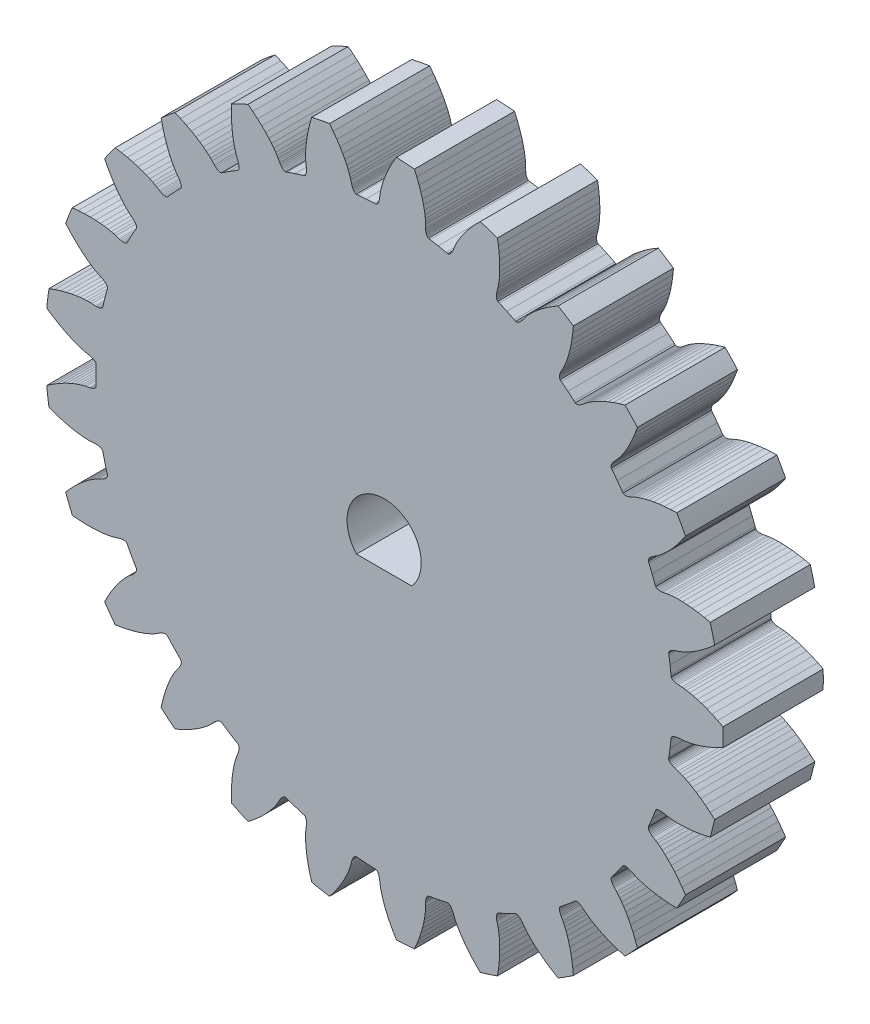
SolidWorks part; units mm, degrees
ref_plane "Front Plane" through (0, 0, 0) normal (0, 0, 1) x (1, 0, 0)
ref_plane "Top Plane" through (0, 0, 0) normal (0, 1, 0) x (1, 0, 0)
ref_plane "Right Plane" through (0, 0, 0) normal (1, 0, 0) x (0, 0, -1)
sketch "Sketch1" plane through (0, 0, 0) normal (0, 0, 1) x (1, 0, 0)
  line L0 (51.4459, 5.2739) -> (51.0519, 4.9541)
  line L1 (51.0519, 4.9541) -> (50.6785, 4.6761)
  line L2 (50.6785, 4.6761) -> (50.3269, 4.4365)
  line L3 (50.3269, 4.4365) -> (50.003, 4.2351)
  line L4 (50.003, 4.2351) -> (49.7071, 4.0679)
  line L5 (49.7071, 4.0679) -> (49.4414, 3.932)
  line L6 (49.4414, 3.932) -> (49.2085, 3.825)
  line L7 (49.2085, 3.825) -> (49.0099, 3.7435)
  line L8 (49.0099, 3.7435) -> (48.8471, 3.6846)
  line L9 (48.8471, 3.6846) -> (48.5824, 3.6)
  line L10 (48.5824, 3.6) -> (48.48, 3.5596)
  line L11 (48.48, 3.5596) -> (48.3896, 3.517)
  line L12 (48.3896, 3.517) -> (48.3112, 3.4725)
  line L13 (48.3112, 3.4725) -> (48.2449, 3.4268)
  line L14 (48.2449, 3.4268) -> (48.1907, 3.3803)
  line L15 (48.1907, 3.3803) -> (48.1486, 3.3335)
  line L16 (48.1486, 3.3335) -> (48.1186, 3.2869)
  line L17 (48.1186, 3.2869) -> (48.1007, 3.2409)
  line L18 (48.1007, 3.2409) -> (48.0947, 3.1961)
  line L19 (48.0947, 3.1961) -> (48.1121, 3.0744)
  line L20 (48.1121, 3.0744) -> (48.2057, 2.4097)
  line L21 (48.2057, 2.4097) -> (48.2803, 1.7426)
  line L22 (48.2803, 1.7426) -> (48.2938, 1.6204)
  line L23 (48.2938, 1.6204) -> (48.3107, 1.5784)
  line L24 (48.3107, 1.5784) -> (48.3395, 1.5384)
  line L25 (48.3395, 1.5384) -> (48.3802, 1.5007)
  line L26 (48.3802, 1.5007) -> (48.4326, 1.4658)
  line L27 (48.4326, 1.4658) -> (48.4966, 1.4342)
  line L28 (48.4966, 1.4342) -> (48.5722, 1.4064)
  line L29 (48.5722, 1.4064) -> (48.6592, 1.3829)
  line L30 (48.6592, 1.3829) -> (48.7573, 1.3641)
  line L31 (48.7573, 1.3641) -> (48.8666, 1.3504)
  line L32 (48.8666, 1.3504) -> (49.144, 1.3343)
  line L33 (49.144, 1.3343) -> (49.3163, 1.3177)
  line L34 (49.3163, 1.3177) -> (49.5289, 1.2882)
  line L35 (49.5289, 1.2882) -> (49.7812, 1.2424)
  line L36 (49.7812, 1.2424) -> (50.0723, 1.1769)
  line L37 (50.0723, 1.1769) -> (50.4005, 1.0885)
  line L38 (50.4005, 1.0885) -> (50.7643, 0.974)
  line L39 (50.7643, 0.974) -> (51.1644, 0.8294)
  line L40 (51.1644, 0.8294) -> (51.5953, 0.653)
  line L41 (51.5953, 0.653) -> (52.0565, 0.4412)
  line L42 (52.0565, 0.4412) -> (52.4946, 0.2183)
  line L43 (52.4946, -1.2438) -> (52.0565, -1.4667)
  line L44 (52.0565, -1.4667) -> (51.5953, -1.6785)
  line L45 (51.5953, -1.6785) -> (51.1644, -1.8549)
  line L46 (51.1644, -1.8549) -> (50.7643, -1.9995)
  line L47 (50.7643, -1.9995) -> (50.4005, -2.114)
  line L48 (50.4005, -2.114) -> (50.0723, -2.2024)
  line L49 (50.0723, -2.2024) -> (49.7812, -2.2679)
  line L50 (49.7812, -2.2679) -> (49.5289, -2.3137)
  line L51 (49.5289, -2.3137) -> (49.3163, -2.3432)
  line L52 (49.3163, -2.3432) -> (49.144, -2.3598)
  line L53 (49.144, -2.3598) -> (48.8666, -2.3759)
  line L54 (48.8666, -2.3759) -> (48.7573, -2.3896)
  line L55 (48.7573, -2.3896) -> (48.6592, -2.4084)
  line L56 (48.6592, -2.4084) -> (48.5722, -2.4319)
  line L57 (48.5722, -2.4319) -> (48.4966, -2.4597)
  line L58 (48.4966, -2.4597) -> (48.4326, -2.4913)
  line L59 (48.4326, -2.4913) -> (48.3802, -2.5262)
  line L60 (48.3802, -2.5262) -> (48.3395, -2.5639)
  line L61 (48.3395, -2.5639) -> (48.3107, -2.6039)
  line L62 (48.3107, -2.6039) -> (48.2938, -2.6459)
  line L63 (48.2938, -2.6459) -> (48.2803, -2.7681)
  line L64 (48.2803, -2.7681) -> (48.2057, -3.4352)
  line L65 (48.2057, -3.4352) -> (48.1121, -4.0999)
  line L66 (48.1121, -4.0999) -> (48.0947, -4.2216)
  line L67 (48.0947, -4.2216) -> (48.1007, -4.2664)
  line L68 (48.1007, -4.2664) -> (48.1186, -4.3124)
  line L69 (48.1186, -4.3124) -> (48.1486, -4.359)
  line L70 (48.1486, -4.359) -> (48.1907, -4.4058)
  line L71 (48.1907, -4.4058) -> (48.2449, -4.4523)
  line L72 (48.2449, -4.4523) -> (48.3112, -4.498)
  line L73 (48.3112, -4.498) -> (48.3896, -4.5425)
  line L74 (48.3896, -4.5425) -> (48.48, -4.5851)
  line L75 (48.48, -4.5851) -> (48.5824, -4.6255)
  line L76 (48.5824, -4.6255) -> (48.8471, -4.7101)
  line L77 (48.8471, -4.7101) -> (49.0099, -4.769)
  line L78 (49.0099, -4.769) -> (49.2085, -4.8505)
  line L79 (49.2085, -4.8505) -> (49.4414, -4.9575)
  line L80 (49.4414, -4.9575) -> (49.7071, -5.0934)
  line L81 (49.7071, -5.0934) -> (50.003, -5.2607)
  line L82 (50.003, -5.2607) -> (50.3269, -5.462)
  line L83 (50.3269, -5.462) -> (50.6785, -5.7016)
  line L84 (50.6785, -5.7016) -> (51.0519, -5.9796)
  line L85 (51.0519, -5.9796) -> (51.4459, -6.2994)
  line L86 (51.4459, -6.2994) -> (51.8149, -6.6243)
  line L87 (51.4513, -8.0404) -> (50.9715, -8.1474)
  line L88 (50.9715, -8.1474) -> (50.4721, -8.2379)
  line L89 (50.4721, -8.2379) -> (50.0109, -8.3016)
  line L90 (50.0109, -8.3016) -> (49.5874, -8.3422)
  line L91 (49.5874, -8.3422) -> (49.2066, -8.3626)
  line L92 (49.2066, -8.3626) -> (48.8667, -8.3666)
  line L93 (48.8667, -8.3666) -> (48.5684, -8.3576)
  line L94 (48.5684, -8.3576) -> (48.3127, -8.3392)
  line L95 (48.3127, -8.3392) -> (48.0995, -8.3149)
  line L96 (48.0995, -8.3149) -> (47.9284, -8.2882)
  line L97 (47.9284, -8.2882) -> (47.6557, -8.2348)
  line L98 (47.6557, -8.2348) -> (47.5465, -8.2208)
  line L99 (47.5465, -8.2208) -> (47.4467, -8.2146)
  line L100 (47.4467, -8.2146) -> (47.3566, -8.2158)
  line L101 (47.3566, -8.2158) -> (47.2765, -8.2239)
  line L102 (47.2765, -8.2239) -> (47.2066, -8.2386)
  line L103 (47.2066, -8.2386) -> (47.1472, -8.2593)
  line L104 (47.1472, -8.2593) -> (47.0984, -8.2857)
  line L105 (47.0984, -8.2857) -> (47.0606, -8.3174)
  line L106 (47.0606, -8.3174) -> (47.0338, -8.3538)
  line L107 (47.0338, -8.3538) -> (46.9903, -8.4688)
  line L108 (46.9903, -8.4688) -> (46.7521, -9.0964)
  line L109 (46.7521, -9.0964) -> (46.4961, -9.7169)
  line L110 (46.4961, -9.7169) -> (46.4491, -9.8305)
  line L111 (46.4491, -9.8305) -> (46.4437, -9.8754)
  line L112 (46.4437, -9.8754) -> (46.4497, -9.9244)
  line L113 (46.4497, -9.9244) -> (46.4671, -9.977)
  line L114 (46.4671, -9.977) -> (46.4963, -10.0328)
  line L115 (46.4963, -10.0328) -> (46.5372, -10.0913)
  line L116 (46.5372, -10.0913) -> (46.59, -10.1521)
  line L117 (46.59, -10.1521) -> (46.6549, -10.2146)
  line L118 (46.6549, -10.2146) -> (46.7318, -10.2784)
  line L119 (46.7318, -10.2784) -> (46.821, -10.343)
  line L120 (46.821, -10.343) -> (47.0563, -10.4908)
  line L121 (47.0563, -10.4908) -> (47.1993, -10.5884)
  line L122 (47.1993, -10.5884) -> (47.3715, -10.7166)
  line L123 (47.3715, -10.7166) -> (47.5704, -10.8782)
  line L124 (47.5704, -10.8782) -> (47.794, -11.0759)
  line L125 (47.794, -11.0759) -> (48.039, -11.3115)
  line L126 (48.039, -11.3115) -> (48.3027, -11.5871)
  line L127 (48.3027, -11.5871) -> (48.5836, -11.9065)
  line L128 (48.5836, -11.9065) -> (48.8762, -12.2687)
  line L129 (48.8762, -12.2687) -> (49.1783, -12.6765)
  line L130 (49.1783, -12.6765) -> (49.4548, -13.0829)
  line L131 (48.7505, -14.3641) -> (48.2591, -14.3484)
  line L132 (48.2591, -14.3484) -> (47.7529, -14.3118)
  line L133 (47.7529, -14.3118) -> (47.2904, -14.2589)
  line L134 (47.2904, -14.2589) -> (46.8702, -14.1928)
  line L135 (46.8702, -14.1928) -> (46.4962, -14.1179)
  line L136 (46.4962, -14.1179) -> (46.166, -14.0372)
  line L137 (46.166, -14.0372) -> (45.8793, -13.9544)
  line L138 (45.8793, -13.9544) -> (45.6362, -13.873)
  line L139 (45.6362, -13.873) -> (45.4357, -13.7964)
  line L140 (45.4357, -13.7964) -> (45.2767, -13.728)
  line L141 (45.2767, -13.728) -> (45.0258, -13.6084)
  line L142 (45.0258, -13.6084) -> (44.9235, -13.5677)
  line L143 (44.9235, -13.5677) -> (44.8284, -13.5369)
  line L144 (44.8284, -13.5369) -> (44.7408, -13.5157)
  line L145 (44.7408, -13.5157) -> (44.6612, -13.5036)
  line L146 (44.6612, -13.5036) -> (44.5899, -13.5004)
  line L147 (44.5899, -13.5004) -> (44.5272, -13.5057)
  line L148 (44.5272, -13.5057) -> (44.4734, -13.5192)
  line L149 (44.4734, -13.5192) -> (44.4288, -13.5404)
  line L150 (44.4288, -13.5404) -> (44.3938, -13.569)
  line L151 (44.3938, -13.569) -> (44.3231, -13.6696)
  line L152 (44.3231, -13.6696) -> (43.9364, -14.2183)
  line L153 (43.9364, -14.2183) -> (43.5341, -14.7556)
  line L154 (43.5341, -14.7556) -> (43.4603, -14.8539)
  line L155 (43.4603, -14.8539) -> (43.4439, -14.8961)
  line L156 (43.4439, -14.8961) -> (43.4375, -14.945)
  line L157 (43.4375, -14.945) -> (43.4413, -15.0003)
  line L158 (43.4413, -15.0003) -> (43.4556, -15.0616)
  line L159 (43.4556, -15.0616) -> (43.4807, -15.1285)
  line L160 (43.4807, -15.1285) -> (43.5168, -15.2005)
  line L161 (43.5168, -15.2005) -> (43.564, -15.2772)
  line L162 (43.564, -15.2772) -> (43.6227, -15.3581)
  line L163 (43.6227, -15.3581) -> (43.693, -15.4429)
  line L164 (43.693, -15.4429) -> (43.8842, -15.6445)
  line L165 (43.8842, -15.6445) -> (43.9985, -15.7746)
  line L166 (43.9985, -15.7746) -> (44.1333, -15.9416)
  line L167 (44.1333, -15.9416) -> (44.2858, -16.1476)
  line L168 (44.2858, -16.1476) -> (44.4532, -16.3947)
  line L169 (44.4532, -16.3947) -> (44.6319, -16.6838)
  line L170 (44.6319, -16.6838) -> (44.8188, -17.0163)
  line L171 (44.8188, -17.0163) -> (45.0115, -17.3956)
  line L172 (45.0115, -17.3956) -> (45.2047, -17.8191)
  line L173 (45.2047, -17.8191) -> (45.3959, -18.2892)
  line L174 (45.3959, -18.2892) -> (45.5627, -18.7517)
  line L175 (44.5619, -19.8175) -> (44.0899, -19.6801)
  line L176 (44.0899, -19.6801) -> (43.6087, -19.5187)
  line L177 (43.6087, -19.5187) -> (43.1739, -19.3524)
  line L178 (43.1739, -19.3524) -> (42.7832, -19.1839)
  line L179 (42.7832, -19.1839) -> (42.4397, -19.0184)
  line L180 (42.4397, -19.0184) -> (42.1399, -18.8581)
  line L181 (42.1399, -18.8581) -> (41.8828, -18.7066)
  line L182 (41.8828, -18.7066) -> (41.6676, -18.5673)
  line L183 (41.6676, -18.5673) -> (41.4924, -18.4432)
  line L184 (41.4924, -18.4432) -> (41.3554, -18.3374)
  line L185 (41.3554, -18.3374) -> (41.1422, -18.1592)
  line L186 (41.1422, -18.1592) -> (41.0532, -18.0944)
  line L187 (41.0532, -18.0944) -> (40.9687, -18.0409)
  line L188 (40.9687, -18.0409) -> (40.8892, -17.9985)
  line L189 (40.8892, -17.9985) -> (40.8151, -17.9671)
  line L190 (40.8151, -17.9671) -> (40.7468, -17.9462)
  line L191 (40.7468, -17.9462) -> (40.6848, -17.9358)
  line L192 (40.6848, -17.9358) -> (40.6293, -17.9354)
  line L193 (40.6293, -17.9354) -> (40.5809, -17.9449)
  line L194 (40.5809, -17.9449) -> (40.5398, -17.9639)
  line L195 (40.5398, -17.9639) -> (40.4463, -18.0437)
  line L196 (40.4463, -18.0437) -> (39.9353, -18.479)
  line L197 (39.9353, -18.479) -> (39.412, -18.8994)
  line L198 (39.412, -18.8994) -> (39.3161, -18.9763)
  line L199 (39.3161, -18.9763) -> (39.2897, -19.013)
  line L200 (39.2897, -19.013) -> (39.2713, -19.0588)
  line L201 (39.2713, -19.0588) -> (39.2613, -19.1134)
  line L202 (39.2613, -19.1134) -> (39.2599, -19.1763)
  line L203 (39.2599, -19.1763) -> (39.2676, -19.2473)
  line L204 (39.2676, -19.2473) -> (39.2846, -19.326)
  line L205 (39.2846, -19.326) -> (39.3113, -19.412)
  line L206 (39.3113, -19.412) -> (39.348, -19.505)
  line L207 (39.348, -19.505) -> (39.3951, -19.6046)
  line L208 (39.3951, -19.6046) -> (39.5301, -19.8474)
  line L209 (39.5301, -19.8474) -> (39.6084, -20.0018)
  line L210 (39.6084, -20.0018) -> (39.6975, -20.1971)
  line L211 (39.6975, -20.1971) -> (39.7939, -20.4346)
  line L212 (39.7939, -20.4346) -> (39.8946, -20.7155)
  line L213 (39.8946, -20.7155) -> (39.9959, -21.04)
  line L214 (39.9959, -21.04) -> (40.0941, -21.4086)
  line L215 (40.0941, -21.4086) -> (40.1864, -21.8238)
  line L216 (40.1864, -21.8238) -> (40.2683, -22.2821)
  line L217 (40.2683, -22.2821) -> (40.3366, -22.785)
  line L218 (40.3366, -22.785) -> (40.3831, -23.2744)
  line L219 (39.1487, -24.0578) -> (38.7257, -23.8073)
  line L220 (38.7257, -23.8073) -> (38.2998, -23.5314)
  line L221 (38.2998, -23.5314) -> (37.9199, -23.2622)
  line L222 (37.9199, -23.2622) -> (37.5835, -23.0019)
  line L223 (37.5835, -23.0019) -> (37.2919, -22.756)
  line L224 (37.2919, -22.756) -> (37.0414, -22.5263)
  line L225 (37.0414, -22.5263) -> (36.83, -22.3156)
  line L226 (36.83, -22.3156) -> (36.6562, -22.1271)
  line L227 (36.6562, -22.1271) -> (36.5174, -21.9634)
  line L228 (36.5174, -21.9634) -> (36.4111, -21.8268)
  line L229 (36.4111, -21.8268) -> (36.2488, -21.6012)
  line L230 (36.2488, -21.6012) -> (36.1788, -21.5163)
  line L231 (36.1788, -21.5163) -> (36.1102, -21.4435)
  line L232 (36.1102, -21.4435) -> (36.0438, -21.3827)
  line L233 (36.0438, -21.3827) -> (35.9798, -21.3338)
  line L234 (35.9798, -21.3338) -> (35.9189, -21.2966)
  line L235 (35.9189, -21.2966) -> (35.8613, -21.271)
  line L236 (35.8613, -21.271) -> (35.8077, -21.2569)
  line L237 (35.8077, -21.2569) -> (35.7584, -21.254)
  line L238 (35.7584, -21.254) -> (35.714, -21.2622)
  line L239 (35.714, -21.2622) -> (35.6036, -21.3163)
  line L240 (35.6036, -21.3163) -> (35.0003, -21.6108)
  line L241 (35.0003, -21.6108) -> (34.3889, -21.8879)
  line L242 (34.3889, -21.8879) -> (34.2769, -21.9385)
  line L243 (34.2769, -21.9385) -> (34.2422, -21.9675)
  line L244 (34.2422, -21.9675) -> (34.213, -22.0073)
  line L245 (34.213, -22.0073) -> (34.1897, -22.0576)
  line L246 (34.1897, -22.0576) -> (34.1728, -22.1183)
  line L247 (34.1728, -22.1183) -> (34.1625, -22.1889)
  line L248 (34.1625, -22.1889) -> (34.1595, -22.2694)
  line L249 (34.1595, -22.2694) -> (34.1639, -22.3593)
  line L250 (34.1639, -22.3593) -> (34.1764, -22.4585)
  line L251 (34.1764, -22.4585) -> (34.1971, -22.5667)
  line L252 (34.1971, -22.5667) -> (34.2676, -22.8355)
  line L253 (34.2676, -22.8355) -> (34.305, -23.0045)
  line L254 (34.305, -23.0045) -> (34.3427, -23.2158)
  line L255 (34.3427, -23.2158) -> (34.3771, -23.4698)
  line L256 (34.3771, -23.4698) -> (34.4047, -23.767)
  line L257 (34.4047, -23.767) -> (34.4221, -24.1065)
  line L258 (34.4221, -24.1065) -> (34.4256, -24.4878)
  line L259 (34.4256, -24.4878) -> (34.4117, -24.913)
  line L260 (34.4117, -24.913) -> (34.3771, -25.3773)
  line L261 (34.3771, -25.3773) -> (34.3182, -25.8814)
  line L262 (34.3182, -25.8814) -> (34.2415, -26.3669)
  line L263 (32.851, -26.8187) -> (32.5036, -26.471)
  line L264 (32.5036, -26.471) -> (32.1597, -26.0978)
  line L265 (32.1597, -26.0978) -> (31.8588, -25.7426)
  line L266 (31.8588, -25.7426) -> (31.5976, -25.4067)
  line L267 (31.5976, -25.4067) -> (31.3763, -25.0961)
  line L268 (31.3763, -25.0961) -> (31.1908, -24.8113)
  line L269 (31.1908, -24.8113) -> (31.0385, -24.5546)
  line L270 (31.0385, -24.5546) -> (30.917, -24.3289)
  line L271 (30.917, -24.3289) -> (30.8233, -24.1358)
  line L272 (30.8233, -24.1358) -> (30.7542, -23.977)
  line L273 (30.7542, -23.977) -> (30.6532, -23.7182)
  line L274 (30.6532, -23.7182) -> (30.6065, -23.6185)
  line L275 (30.6065, -23.6185) -> (30.5582, -23.5309)
  line L276 (30.5582, -23.5309) -> (30.5089, -23.4555)
  line L277 (30.5089, -23.4555) -> (30.4592, -23.3922)
  line L278 (30.4592, -23.3922) -> (30.4094, -23.3411)
  line L279 (30.4094, -23.3411) -> (30.36, -23.302)
  line L280 (30.36, -23.302) -> (30.3116, -23.275)
  line L281 (30.3116, -23.275) -> (30.2646, -23.2599)
  line L282 (30.2646, -23.2599) -> (30.2195, -23.2568)
  line L283 (30.2195, -23.2568) -> (30.0991, -23.2818)
  line L284 (30.0991, -23.2818) -> (29.4416, -23.4169)
  line L285 (29.4416, -23.4169) -> (28.7805, -23.5333)
  line L286 (28.7805, -23.5333) -> (28.6593, -23.5544)
  line L287 (28.6593, -23.5544) -> (28.6185, -23.5739)
  line L288 (28.6185, -23.5739) -> (28.5804, -23.6052)
  line L289 (28.5804, -23.6052) -> (28.5453, -23.6482)
  line L290 (28.5453, -23.6482) -> (28.5138, -23.7027)
  line L291 (28.5138, -23.7027) -> (28.4863, -23.7686)
  line L292 (28.4863, -23.7686) -> (28.4633, -23.8457)
  line L293 (28.4633, -23.8457) -> (28.4453, -23.934)
  line L294 (28.4453, -23.934) -> (28.4326, -24.0332)
  line L295 (28.4326, -24.0332) -> (28.4259, -24.1431)
  line L296 (28.4259, -24.1431) -> (28.4272, -24.4209)
  line L297 (28.4272, -24.4209) -> (28.4215, -24.594)
  line L298 (28.4215, -24.594) -> (28.4054, -24.808)
  line L299 (28.4054, -24.808) -> (28.3756, -25.0626)
  line L300 (28.3756, -25.0626) -> (28.3285, -25.3573)
  line L301 (28.3285, -25.3573) -> (28.2608, -25.6904)
  line L302 (28.2608, -25.6904) -> (28.1694, -26.0607)
  line L303 (28.1694, -26.0607) -> (28.0502, -26.4691)
  line L304 (28.0502, -26.4691) -> (27.9012, -26.9101)
  line L305 (27.9012, -26.9101) -> (27.7188, -27.3837)
  line L306 (27.7188, -27.3837) -> (27.5238, -27.835)
  line L307 (26.0646, -27.9268) -> (25.8146, -27.5035)
  line L308 (25.8146, -27.5035) -> (25.5743, -27.0565)
  line L309 (25.5743, -27.0565) -> (25.3711, -26.6376)
  line L310 (25.3711, -26.6376) -> (25.2017, -26.2474)
  line L311 (25.2017, -26.2474) -> (25.0646, -25.8915)
  line L312 (25.0646, -25.8915) -> (24.9558, -25.5695)
  line L313 (24.9558, -25.5695) -> (24.8721, -25.283)
  line L314 (24.8721, -25.283) -> (24.8106, -25.0342)
  line L315 (24.8106, -25.0342) -> (24.7678, -24.8238)
  line L316 (24.7678, -24.8238) -> (24.7404, -24.6529)
  line L317 (24.7404, -24.6529) -> (24.7069, -24.377)
  line L318 (24.7069, -24.377) -> (24.6864, -24.2688)
  line L319 (24.6864, -24.2688) -> (24.6615, -24.172)
  line L320 (24.6615, -24.172) -> (24.6325, -24.0867)
  line L321 (24.6325, -24.0867) -> (24.6, -24.0131)
  line L322 (24.6, -24.0131) -> (24.5645, -23.9511)
  line L323 (24.5645, -23.9511) -> (24.5264, -23.901)
  line L324 (24.5264, -23.901) -> (24.4862, -23.8628)
  line L325 (24.4862, -23.8628) -> (24.4445, -23.8366)
  line L326 (24.4445, -23.8366) -> (24.4015, -23.8223)
  line L327 (24.4015, -23.8223) -> (24.2787, -23.8165)
  line L328 (24.2787, -23.8165) -> (23.6083, -23.7839)
  line L329 (23.6083, -23.7839) -> (22.939, -23.7322)
  line L330 (22.939, -23.7322) -> (22.8164, -23.7226)
  line L331 (22.8164, -23.7226) -> (22.7721, -23.7313)
  line L332 (22.7721, -23.7313) -> (22.7273, -23.7521)
  line L333 (22.7273, -23.7521) -> (22.6826, -23.785)
  line L334 (22.6826, -23.785) -> (22.6386, -23.83)
  line L335 (22.6386, -23.83) -> (22.5956, -23.8869)
  line L336 (22.5956, -23.8869) -> (22.5541, -23.956)
  line L337 (22.5541, -23.956) -> (22.5147, -24.037)
  line L338 (22.5147, -24.037) -> (22.4778, -24.1299)
  line L339 (22.4778, -24.1299) -> (22.4439, -24.2347)
  line L340 (22.4439, -24.2347) -> (22.3761, -24.5041)
  line L341 (22.3761, -24.5041) -> (22.3275, -24.6703)
  line L342 (22.3275, -24.6703) -> (22.2587, -24.8736)
  line L343 (22.2587, -24.8736) -> (22.1665, -25.1128)
  line L344 (22.1665, -25.1128) -> (22.0476, -25.3865)
  line L345 (22.0476, -25.3865) -> (21.8992, -25.6923)
  line L346 (21.8992, -25.6923) -> (21.7186, -26.0283)
  line L347 (21.7186, -26.0283) -> (21.5016, -26.3942)
  line L348 (21.5016, -26.3942) -> (21.2476, -26.7843)
  line L349 (21.2476, -26.7843) -> (20.9531, -27.1976)
  line L350 (20.9531, -27.1976) -> (20.652, -27.5862)
  line L351 (19.2159, -27.3123) -> (19.079, -26.8401)
  line L352 (19.079, -26.8401) -> (18.9573, -26.3474)
  line L353 (18.9573, -26.3474) -> (18.8648, -25.8912)
  line L354 (18.8648, -25.8912) -> (18.7977, -25.4711)
  line L355 (18.7977, -25.4711) -> (18.7534, -25.0922)
  line L356 (18.7534, -25.0922) -> (18.7281, -24.7533)
  line L357 (18.7281, -24.7533) -> (18.7183, -24.455)
  line L358 (18.7183, -24.455) -> (18.7206, -24.1987)
  line L359 (18.7206, -24.1987) -> (18.7315, -23.9843)
  line L360 (18.7315, -23.9843) -> (18.7474, -23.8119)
  line L361 (18.7474, -23.8119) -> (18.7836, -23.5364)
  line L362 (18.7836, -23.5364) -> (18.7907, -23.4265)
  line L363 (18.7907, -23.4265) -> (18.7906, -23.3266)
  line L364 (18.7906, -23.3266) -> (18.7837, -23.2367)
  line L365 (18.7837, -23.2367) -> (18.7706, -23.1573)
  line L366 (18.7706, -23.1573) -> (18.7516, -23.0885)
  line L367 (18.7516, -23.0885) -> (18.7272, -23.0305)
  line L368 (18.7272, -23.0305) -> (18.6977, -22.9835)
  line L369 (18.6977, -22.9835) -> (18.6638, -22.9476)
  line L370 (18.6638, -22.9476) -> (18.6258, -22.9232)
  line L371 (18.6258, -22.9232) -> (18.5082, -22.887)
  line L372 (18.5082, -22.887) -> (17.8669, -22.6887)
  line L373 (17.8669, -22.6887) -> (17.2316, -22.4722)
  line L374 (17.2316, -22.4722) -> (17.1152, -22.4324)
  line L375 (17.1152, -22.4324) -> (17.0701, -22.4298)
  line L376 (17.0701, -22.4298) -> (17.0216, -22.4388)
  line L377 (17.0216, -22.4388) -> (16.9701, -22.4596)
  line L378 (16.9701, -22.4596) -> (16.9163, -22.4921)
  line L379 (16.9163, -22.4921) -> (16.8604, -22.5367)
  line L380 (16.8604, -22.5367) -> (16.8031, -22.5932)
  line L381 (16.8031, -22.5932) -> (16.7448, -22.6619)
  line L382 (16.7448, -22.6619) -> (16.686, -22.7427)
  line L383 (16.686, -22.7427) -> (16.6271, -22.8357)
  line L384 (16.6271, -22.8357) -> (16.4944, -23.0799)
  line L385 (16.4944, -23.0799) -> (16.406, -23.2287)
  line L386 (16.406, -23.2287) -> (16.2888, -23.4086)
  line L387 (16.2888, -23.4086) -> (16.14, -23.6173)
  line L388 (16.14, -23.6173) -> (15.9568, -23.8528)
  line L389 (15.9568, -23.8528) -> (15.737, -24.1122)
  line L390 (15.737, -24.1122) -> (15.4785, -24.3926)
  line L391 (15.4785, -24.3926) -> (15.1773, -24.6931)
  line L392 (15.1773, -24.6931) -> (14.8343, -25.0078)
  line L393 (14.8343, -25.0078) -> (14.4462, -25.3349)
  line L394 (14.4462, -25.3349) -> (14.058, -25.6364)
  line L395 (12.7351, -25.0139) -> (12.7199, -24.5225)
  line L396 (12.7199, -24.5225) -> (12.7246, -24.015)
  line L397 (12.7246, -24.015) -> (12.7484, -23.5501)
  line L398 (12.7484, -23.5501) -> (12.788, -23.1265)
  line L399 (12.788, -23.1265) -> (12.8393, -22.7486)
  line L400 (12.8393, -22.7486) -> (12.899, -22.414)
  line L401 (12.899, -22.414) -> (12.9637, -22.1226)
  line L402 (12.9637, -22.1226) -> (13.0297, -21.8749)
  line L403 (13.0297, -21.8749) -> (13.0935, -21.67)
  line L404 (13.0935, -21.67) -> (13.1519, -21.507)
  line L405 (13.1519, -21.507) -> (13.2554, -21.2491)
  line L406 (13.2554, -21.2491) -> (13.2896, -21.1445)
  line L407 (13.2896, -21.1445) -> (13.3144, -21.0476)
  line L408 (13.3144, -21.0476) -> (13.3301, -20.9589)
  line L409 (13.3301, -20.9589) -> (13.3371, -20.8787)
  line L410 (13.3371, -20.8787) -> (13.3358, -20.8073)
  line L411 (13.3358, -20.8073) -> (13.3266, -20.745)
  line L412 (13.3266, -20.745) -> (13.3098, -20.6922)
  line L413 (13.3098, -20.6922) -> (13.2858, -20.6491)
  line L414 (13.2858, -20.6491) -> (13.255, -20.6159)
  line L415 (13.255, -20.6159) -> (13.1502, -20.5517)
  line L416 (13.1502, -20.5517) -> (12.5784, -20.2001)
  line L417 (12.5784, -20.2001) -> (12.0168, -19.8324)
  line L418 (12.0168, -19.8324) -> (11.914, -19.7649)
  line L419 (11.914, -19.7649) -> (11.8709, -19.7512)
  line L420 (11.8709, -19.7512) -> (11.8217, -19.7478)
  line L421 (11.8217, -19.7478) -> (11.7667, -19.7551)
  line L422 (11.7667, -19.7551) -> (11.7065, -19.7733)
  line L423 (11.7065, -19.7733) -> (11.6413, -19.8025)
  line L424 (11.6413, -19.8025) -> (11.5717, -19.843)
  line L425 (11.5717, -19.843) -> (11.4982, -19.895)
  line L426 (11.4982, -19.895) -> (11.4211, -19.9587)
  line L427 (11.4211, -19.9587) -> (11.3409, -20.0341)
  line L428 (11.3409, -20.0341) -> (11.1517, -20.2376)
  line L429 (11.1517, -20.2376) -> (11.029, -20.3598)
  line L430 (11.029, -20.3598) -> (10.8708, -20.5049)
  line L431 (10.8708, -20.5049) -> (10.6748, -20.67)
  line L432 (10.6748, -20.67) -> (10.4387, -20.8526)
  line L433 (10.4387, -20.8526) -> (10.1614, -21.0491)
  line L434 (10.1614, -21.0491) -> (9.8412, -21.2565)
  line L435 (9.8412, -21.2565) -> (9.4748, -21.4726)
  line L436 (9.4748, -21.4726) -> (9.0642, -21.6921)
  line L437 (9.0642, -21.6921) -> (8.6071, -21.9124)
  line L438 (8.6071, -21.9124) -> (8.156, -22.1079)
  line L439 (7.0295, -21.176) -> (7.137, -20.6963)
  line L440 (7.137, -20.6963) -> (7.2678, -20.2059)
  line L441 (7.2678, -20.2059) -> (7.4065, -19.7615)
  line L442 (7.4065, -19.7615) -> (7.5501, -19.3611)
  line L443 (7.5501, -19.3611) -> (7.6938, -19.0078)
  line L444 (7.6938, -19.0078) -> (7.8349, -18.6985)
  line L445 (7.8349, -18.6985) -> (7.97, -18.4324)
  line L446 (7.97, -18.4324) -> (8.0955, -18.2089)
  line L447 (8.0955, -18.2089) -> (8.2083, -18.0263)
  line L448 (8.2083, -18.0263) -> (8.3053, -17.8829)
  line L449 (8.3053, -17.8829) -> (8.4697, -17.6589)
  line L450 (8.4697, -17.6589) -> (8.5289, -17.566)
  line L451 (8.5289, -17.566) -> (8.5769, -17.4784)
  line L452 (8.5769, -17.4784) -> (8.6142, -17.3964)
  line L453 (8.6142, -17.3964) -> (8.641, -17.3204)
  line L454 (8.641, -17.3204) -> (8.6575, -17.251)
  line L455 (8.6575, -17.251) -> (8.664, -17.1883)
  line L456 (8.664, -17.1883) -> (8.6609, -17.133)
  line L457 (8.6609, -17.133) -> (8.6484, -17.0852)
  line L458 (8.6484, -17.0852) -> (8.6269, -17.0455)
  line L459 (8.6269, -17.0455) -> (8.5413, -16.9572)
  line L460 (8.5413, -16.9572) -> (8.0748, -16.4745)
  line L461 (8.0748, -16.4745) -> (7.6224, -15.9786)
  line L462 (7.6224, -15.9786) -> (7.5396, -15.8877)
  line L463 (7.5396, -15.8877) -> (7.5013, -15.8637)
  line L464 (7.5013, -15.8637) -> (7.4544, -15.8482)
  line L465 (7.4544, -15.8482) -> (7.3994, -15.8416)
  line L466 (7.3994, -15.8416) -> (7.3365, -15.8442)
  line L467 (7.3365, -15.8442) -> (7.2661, -15.8563)
  line L468 (7.2661, -15.8563) -> (7.1887, -15.8783)
  line L469 (7.1887, -15.8783) -> (7.1045, -15.9103)
  line L470 (7.1045, -15.9103) -> (7.014, -15.9528)
  line L471 (7.014, -15.9528) -> (6.9175, -16.006)
  line L472 (6.9175, -16.006) -> (6.6836, -16.156)
  line L473 (6.6836, -16.156) -> (6.5345, -16.2439)
  line L474 (6.5345, -16.2439) -> (6.3451, -16.345)
  line L475 (6.3451, -16.345) -> (6.1142, -16.4562)
  line L476 (6.1142, -16.4562) -> (5.8401, -16.5743)
  line L477 (5.8401, -16.5743) -> (5.5226, -16.6957)
  line L478 (5.5226, -16.6957) -> (5.161, -16.817)
  line L479 (5.161, -16.817) -> (4.7523, -16.9351)
  line L480 (4.7523, -16.9351) -> (4.3001, -17.0456)
  line L481 (4.3001, -17.0456) -> (3.8025, -17.1454)
  line L482 (3.8025, -17.1454) -> (3.317, -17.2226)
  line L483 (2.4576, -16.0397) -> (2.681, -15.6018)
  line L484 (2.681, -15.6018) -> (2.9296, -15.1594)
  line L485 (2.9296, -15.1594) -> (3.1745, -14.7634)
  line L486 (3.1745, -14.7634) -> (3.4132, -14.4113)
  line L487 (3.4132, -14.4113) -> (3.6402, -14.1048)
  line L488 (3.6402, -14.1048) -> (3.8538, -13.8404)
  line L489 (3.8538, -13.8404) -> (4.0508, -13.6162)
  line L490 (4.0508, -13.6162) -> (4.228, -13.431)
  line L491 (4.228, -13.431) -> (4.3826, -13.2822)
  line L492 (4.3826, -13.2822) -> (4.5123, -13.1674)
  line L493 (4.5123, -13.1674) -> (4.7273, -12.9913)
  line L494 (4.7273, -12.9913) -> (4.8076, -12.9161)
  line L495 (4.8076, -12.9161) -> (4.876, -12.8431)
  line L496 (4.876, -12.8431) -> (4.9325, -12.773)
  line L497 (4.9325, -12.773) -> (4.9773, -12.7061)
  line L498 (4.9773, -12.7061) -> (5.0106, -12.6429)
  line L499 (5.0106, -12.6429) -> (5.0325, -12.5839)
  line L500 (5.0325, -12.5839) -> (5.0432, -12.5295)
  line L501 (5.0432, -12.5295) -> (5.043, -12.4801)
  line L502 (5.043, -12.4801) -> (5.032, -12.4362)
  line L503 (5.032, -12.4362) -> (4.9711, -12.3295)
  line L504 (4.9711, -12.3295) -> (4.6393, -11.7459)
  line L505 (4.6393, -11.7459) -> (4.3244, -11.1531)
  line L506 (4.3244, -11.1531) -> (4.2669, -11.0445)
  line L507 (4.2669, -11.0445) -> (4.2357, -11.0117)
  line L508 (4.2357, -11.0117) -> (4.1942, -10.985)
  line L509 (4.1942, -10.985) -> (4.1425, -10.965)
  line L510 (4.1425, -10.965) -> (4.0809, -10.9518)
  line L511 (4.0809, -10.9518) -> (4.0097, -10.9461)
  line L512 (4.0097, -10.9461) -> (3.9293, -10.948)
  line L513 (3.9293, -10.948) -> (3.8397, -10.9582)
  line L514 (3.8397, -10.9582) -> (3.7415, -10.9768)
  line L515 (3.7415, -10.9768) -> (3.6349, -11.0043)
  line L516 (3.6349, -11.0043) -> (3.371, -11.0915)
  line L517 (3.371, -11.0915) -> (3.2047, -11.1395)
  line L518 (3.2047, -11.1395) -> (2.9962, -11.1903)
  line L519 (2.9962, -11.1903) -> (2.7448, -11.2406)
  line L520 (2.7448, -11.2406) -> (2.45, -11.2869)
  line L521 (2.45, -11.2869) -> (2.1123, -11.3255)
  line L522 (2.1123, -11.3255) -> (1.7319, -11.353)
  line L523 (1.7319, -11.353) -> (1.3066, -11.3658)
  line L524 (1.3066, -11.3658) -> (0.8411, -11.3604)
  line L525 (0.8411, -11.3604) -> (0.3343, -11.3332)
  line L526 (0.3343, -11.3332) -> (-0.1551, -11.2872)
  line L527 (-0.6933, -9.9279) -> (-0.368, -9.5593)
  line L528 (-0.368, -9.5593) -> (-0.0172, -9.1926)
  line L529 (-0.0172, -9.1926) -> (0.3185, -8.87)
  line L530 (0.3185, -8.87) -> (0.6372, -8.5882)
  line L531 (0.6372, -8.5882) -> (0.9333, -8.3479)
  line L532 (0.9333, -8.3479) -> (1.206, -8.1448)
  line L533 (1.206, -8.1448) -> (1.4526, -7.9767)
  line L534 (1.4526, -7.9767) -> (1.6702, -7.8413)
  line L535 (1.6702, -7.8413) -> (1.857, -7.7357)
  line L536 (1.857, -7.7357) -> (2.0111, -7.6568)
  line L537 (2.0111, -7.6568) -> (2.2632, -7.5397)
  line L538 (2.2632, -7.5397) -> (2.3597, -7.4868)
  line L539 (2.3597, -7.4868) -> (2.4441, -7.4331)
  line L540 (2.4441, -7.4331) -> (2.5163, -7.3792)
  line L541 (2.5163, -7.3792) -> (2.5763, -7.3256)
  line L542 (2.5763, -7.3256) -> (2.6242, -7.2726)
  line L543 (2.6242, -7.2726) -> (2.6601, -7.2209)
  line L544 (2.6601, -7.2209) -> (2.684, -7.1709)
  line L545 (2.684, -7.1709) -> (2.6961, -7.123)
  line L546 (2.6961, -7.123) -> (2.6964, -7.0778)
  line L547 (2.6964, -7.0778) -> (2.6639, -6.9592)
  line L548 (2.6639, -6.9592) -> (2.4877, -6.3115)
  line L549 (2.4877, -6.3115) -> (2.3301, -5.659)
  line L550 (2.3301, -5.659) -> (2.3014, -5.5395)
  line L551 (2.3014, -5.5395) -> (2.2793, -5.5)
  line L552 (2.2793, -5.5) -> (2.2457, -5.4638)
  line L553 (2.2457, -5.4638) -> (2.2007, -5.4315)
  line L554 (2.2007, -5.4315) -> (2.1443, -5.4035)
  line L555 (2.1443, -5.4035) -> (2.0768, -5.3802)
  line L556 (2.0768, -5.3802) -> (1.9984, -5.3621)
  line L557 (1.9984, -5.3621) -> (1.9091, -5.3497)
  line L558 (1.9091, -5.3497) -> (1.8094, -5.3433)
  line L559 (1.8094, -5.3433) -> (1.6992, -5.3434)
  line L560 (1.6992, -5.3434) -> (1.422, -5.3622)
  line L561 (1.422, -5.3622) -> (1.2489, -5.3673)
  line L562 (1.2489, -5.3673) -> (1.0343, -5.3647)
  line L563 (1.0343, -5.3647) -> (0.7784, -5.3509)
  line L564 (0.7784, -5.3509) -> (0.4813, -5.3224)
  line L565 (0.4813, -5.3224) -> (0.1446, -5.2759)
  line L566 (0.1446, -5.2759) -> (-0.2307, -5.2079)
  line L567 (-0.2307, -5.2079) -> (-0.6458, -5.1146)
  line L568 (-0.6458, -5.1146) -> (-1.0953, -4.9935)
  line L569 (-1.0953, -4.9935) -> (-1.5794, -4.8412)
  line L570 (-1.5794, -4.8412) -> (-2.042, -4.6749)
  line L571 (-2.2253, -3.2244) -> (-1.8185, -2.9483)
  line L572 (-1.8185, -2.9483) -> (-1.3875, -2.6804)
  line L573 (-1.3875, -2.6804) -> (-0.9822, -2.4514)
  line L574 (-0.9822, -2.4514) -> (-0.6034, -2.2578)
  line L575 (-0.6034, -2.2578) -> (-0.2568, -2.0986)
  line L576 (-0.2568, -2.0986) -> (0.0578, -1.9697)
  line L577 (0.0578, -1.9697) -> (0.3384, -1.8682)
  line L578 (0.3384, -1.8682) -> (0.5829, -1.7912)
  line L579 (0.5829, -1.7912) -> (0.7901, -1.7353)
  line L580 (0.7901, -1.7353) -> (0.959, -1.6972)
  line L581 (0.959, -1.6972) -> (1.2322, -1.6465)
  line L582 (1.2322, -1.6465) -> (1.3389, -1.6193)
  line L583 (1.3389, -1.6193) -> (1.434, -1.5883)
  line L584 (1.434, -1.5883) -> (1.5173, -1.554)
  line L585 (1.5173, -1.554) -> (1.5888, -1.517)
  line L586 (1.5888, -1.517) -> (1.6483, -1.4776)
  line L587 (1.6483, -1.4776) -> (1.696, -1.4365)
  line L588 (1.696, -1.4365) -> (1.7316, -1.394)
  line L589 (1.7316, -1.394) -> (1.7552, -1.3506)
  line L590 (1.7552, -1.3506) -> (1.7667, -1.3069)
  line L591 (1.7667, -1.3069) -> (1.7647, -1.1839)
  line L592 (1.7647, -1.1839) -> (1.7552, -0.5128)
  line L593 (1.7552, -0.5128) -> (1.7647, 0.1584)
  line L594 (1.7647, 0.1584) -> (1.7667, 0.2814)
  line L595 (1.7667, 0.2814) -> (1.7552, 0.3251)
  line L596 (1.7552, 0.3251) -> (1.7316, 0.3685)
  line L597 (1.7316, 0.3685) -> (1.696, 0.411)
  line L598 (1.696, 0.411) -> (1.6483, 0.4521)
  line L599 (1.6483, 0.4521) -> (1.5888, 0.4915)
  line L600 (1.5888, 0.4915) -> (1.5173, 0.5285)
  line L601 (1.5173, 0.5285) -> (1.434, 0.5628)
  line L602 (1.434, 0.5628) -> (1.3389, 0.5938)
  line L603 (1.3389, 0.5938) -> (1.2322, 0.621)
  line L604 (1.2322, 0.621) -> (0.959, 0.6717)
  line L605 (0.959, 0.6717) -> (0.7901, 0.7098)
  line L606 (0.7901, 0.7098) -> (0.5829, 0.7657)
  line L607 (0.5829, 0.7657) -> (0.3384, 0.8427)
  line L608 (0.3384, 0.8427) -> (0.0578, 0.9442)
  line L609 (0.0578, 0.9442) -> (-0.2568, 1.0731)
  line L610 (-0.2568, 1.0731) -> (-0.6034, 1.2323)
  line L611 (-0.6034, 1.2323) -> (-0.9822, 1.4258)
  line L612 (-0.9822, 1.4258) -> (-1.3875, 1.6549)
  line L613 (-1.3875, 1.6549) -> (-1.8185, 1.9228)
  line L614 (-1.8185, 1.9228) -> (-2.2253, 2.1989)
  line L615 (-2.042, 3.6494) -> (-1.5794, 3.8157)
  line L616 (-1.5794, 3.8157) -> (-1.0953, 3.968)
  line L617 (-1.0953, 3.968) -> (-0.6458, 4.0891)
  line L618 (-0.6458, 4.0891) -> (-0.2307, 4.1824)
  line L619 (-0.2307, 4.1824) -> (0.1446, 4.2503)
  line L620 (0.1446, 4.2503) -> (0.4813, 4.2969)
  line L621 (0.4813, 4.2969) -> (0.7784, 4.3254)
  line L622 (0.7784, 4.3254) -> (1.0343, 4.3392)
  line L623 (1.0343, 4.3392) -> (1.2489, 4.3418)
  line L624 (1.2489, 4.3418) -> (1.422, 4.3367)
  line L625 (1.422, 4.3367) -> (1.6992, 4.3179)
  line L626 (1.6992, 4.3179) -> (1.8094, 4.3178)
  line L627 (1.8094, 4.3178) -> (1.9091, 4.3241)
  line L628 (1.9091, 4.3241) -> (1.9984, 4.3366)
  line L629 (1.9984, 4.3366) -> (2.0768, 4.3547)
  line L630 (2.0768, 4.3547) -> (2.1443, 4.378)
  line L631 (2.1443, 4.378) -> (2.2007, 4.406)
  line L632 (2.2007, 4.406) -> (2.2457, 4.4383)
  line L633 (2.2457, 4.4383) -> (2.2793, 4.4745)
  line L634 (2.2793, 4.4745) -> (2.3014, 4.514)
  line L635 (2.3014, 4.514) -> (2.3301, 4.6335)
  line L636 (2.3301, 4.6335) -> (2.4877, 5.286)
  line L637 (2.4877, 5.286) -> (2.6639, 5.9337)
  line L638 (2.6639, 5.9337) -> (2.6964, 6.0523)
  line L639 (2.6964, 6.0523) -> (2.6961, 6.0975)
  line L640 (2.6961, 6.0975) -> (2.684, 6.1454)
  line L641 (2.684, 6.1454) -> (2.6601, 6.1954)
  line L642 (2.6601, 6.1954) -> (2.6242, 6.2471)
  line L643 (2.6242, 6.2471) -> (2.5763, 6.3001)
  line L644 (2.5763, 6.3001) -> (2.5163, 6.3537)
  line L645 (2.5163, 6.3537) -> (2.4441, 6.4076)
  line L646 (2.4441, 6.4076) -> (2.3597, 6.4613)
  line L647 (2.3597, 6.4613) -> (2.2632, 6.5142)
  line L648 (2.2632, 6.5142) -> (2.0111, 6.6313)
  line L649 (2.0111, 6.6313) -> (1.857, 6.7101)
  line L650 (1.857, 6.7101) -> (1.6702, 6.8158)
  line L651 (1.6702, 6.8158) -> (1.4526, 6.9512)
  line L652 (1.4526, 6.9512) -> (1.206, 7.1193)
  line L653 (1.206, 7.1193) -> (0.9333, 7.3224)
  line L654 (0.9333, 7.3224) -> (0.6372, 7.5627)
  line L655 (0.6372, 7.5627) -> (0.3185, 7.8444)
  line L656 (0.3185, 7.8444) -> (-0.0172, 8.1671)
  line L657 (-0.0172, 8.1671) -> (-0.368, 8.5338)
  line L658 (-0.368, 8.5338) -> (-0.6933, 8.9024)
  line L659 (-0.1551, 10.2617) -> (0.3343, 10.3077)
  line L660 (0.3343, 10.3077) -> (0.8411, 10.3349)
  line L661 (0.8411, 10.3349) -> (1.3066, 10.3403)
  line L662 (1.3066, 10.3403) -> (1.7319, 10.3275)
  line L663 (1.7319, 10.3275) -> (2.1123, 10.3)
  line L664 (2.1123, 10.3) -> (2.45, 10.2614)
  line L665 (2.45, 10.2614) -> (2.7448, 10.2151)
  line L666 (2.7448, 10.2151) -> (2.9962, 10.1648)
  line L667 (2.9962, 10.1648) -> (3.2047, 10.114)
  line L668 (3.2047, 10.114) -> (3.371, 10.066)
  line L669 (3.371, 10.066) -> (3.6349, 9.9788)
  line L670 (3.6349, 9.9788) -> (3.7415, 9.9513)
  line L671 (3.7415, 9.9513) -> (3.8397, 9.9326)
  line L672 (3.8397, 9.9326) -> (3.9293, 9.9225)
  line L673 (3.9293, 9.9225) -> (4.0097, 9.9205)
  line L674 (4.0097, 9.9205) -> (4.0809, 9.9263)
  line L675 (4.0809, 9.9263) -> (4.1425, 9.9394)
  line L676 (4.1425, 9.9394) -> (4.1942, 9.9595)
  line L677 (4.1942, 9.9595) -> (4.2357, 9.9862)
  line L678 (4.2357, 9.9862) -> (4.2669, 10.0189)
  line L679 (4.2669, 10.0189) -> (4.3244, 10.1276)
  line L680 (4.3244, 10.1276) -> (4.6393, 10.7204)
  line L681 (4.6393, 10.7204) -> (4.9711, 11.3039)
  line L682 (4.9711, 11.3039) -> (5.032, 11.4107)
  line L683 (5.032, 11.4107) -> (5.043, 11.4546)
  line L684 (5.043, 11.4546) -> (5.0432, 11.504)
  line L685 (5.0432, 11.504) -> (5.0325, 11.5584)
  line L686 (5.0325, 11.5584) -> (5.0106, 11.6174)
  line L687 (5.0106, 11.6174) -> (4.9773, 11.6806)
  line L688 (4.9773, 11.6806) -> (4.9325, 11.7475)
  line L689 (4.9325, 11.7475) -> (4.876, 11.8176)
  line L690 (4.876, 11.8176) -> (4.8076, 11.8906)
  line L691 (4.8076, 11.8906) -> (4.7273, 11.9658)
  line L692 (4.7273, 11.9658) -> (4.5123, 12.1419)
  line L693 (4.5123, 12.1419) -> (4.3826, 12.2566)
  line L694 (4.3826, 12.2566) -> (4.228, 12.4055)
  line L695 (4.228, 12.4055) -> (4.0508, 12.5907)
  line L696 (4.0508, 12.5907) -> (3.8538, 12.8149)
  line L697 (3.8538, 12.8149) -> (3.6402, 13.0793)
  line L698 (3.6402, 13.0793) -> (3.4132, 13.3858)
  line L699 (3.4132, 13.3858) -> (3.1745, 13.7379)
  line L700 (3.1745, 13.7379) -> (2.9296, 14.1339)
  line L701 (2.9296, 14.1339) -> (2.681, 14.5763)
  line L702 (2.681, 14.5763) -> (2.4576, 15.0142)
  line L703 (3.317, 16.197) -> (3.8025, 16.1199)
  line L704 (3.8025, 16.1199) -> (4.3001, 16.0201)
  line L705 (4.3001, 16.0201) -> (4.7523, 15.9096)
  line L706 (4.7523, 15.9096) -> (5.161, 15.7914)
  line L707 (5.161, 15.7914) -> (5.5226, 15.6702)
  line L708 (5.5226, 15.6702) -> (5.8401, 15.5488)
  line L709 (5.8401, 15.5488) -> (6.1142, 15.4307)
  line L710 (6.1142, 15.4307) -> (6.3451, 15.3195)
  line L711 (6.3451, 15.3195) -> (6.5345, 15.2184)
  line L712 (6.5345, 15.2184) -> (6.6836, 15.1305)
  line L713 (6.6836, 15.1305) -> (6.9175, 14.9805)
  line L714 (6.9175, 14.9805) -> (7.014, 14.9273)
  line L715 (7.014, 14.9273) -> (7.1045, 14.8848)
  line L716 (7.1045, 14.8848) -> (7.1887, 14.8528)
  line L717 (7.1887, 14.8528) -> (7.2661, 14.8308)
  line L718 (7.2661, 14.8308) -> (7.3365, 14.8187)
  line L719 (7.3365, 14.8187) -> (7.3994, 14.8161)
  line L720 (7.3994, 14.8161) -> (7.4544, 14.8227)
  line L721 (7.4544, 14.8227) -> (7.5013, 14.8382)
  line L722 (7.5013, 14.8382) -> (7.5396, 14.8622)
  line L723 (7.5396, 14.8622) -> (7.6224, 14.9531)
  line L724 (7.6224, 14.9531) -> (8.0748, 15.449)
  line L725 (8.0748, 15.449) -> (8.5413, 15.9317)
  line L726 (8.5413, 15.9317) -> (8.6269, 16.02)
  line L727 (8.6269, 16.02) -> (8.6484, 16.0597)
  line L728 (8.6484, 16.0597) -> (8.6609, 16.1075)
  line L729 (8.6609, 16.1075) -> (8.664, 16.1628)
  line L730 (8.664, 16.1628) -> (8.6575, 16.2254)
  line L731 (8.6575, 16.2254) -> (8.641, 16.2949)
  line L732 (8.641, 16.2949) -> (8.6142, 16.3709)
  line L733 (8.6142, 16.3709) -> (8.5769, 16.4529)
  line L734 (8.5769, 16.4529) -> (8.5289, 16.5405)
  line L735 (8.5289, 16.5405) -> (8.4697, 16.6334)
  line L736 (8.4697, 16.6334) -> (8.3053, 16.8574)
  line L737 (8.3053, 16.8574) -> (8.2083, 17.0008)
  line L738 (8.2083, 17.0008) -> (8.0955, 17.1834)
  line L739 (8.0955, 17.1834) -> (7.97, 17.4069)
  line L740 (7.97, 17.4069) -> (7.8349, 17.673)
  line L741 (7.8349, 17.673) -> (7.6938, 17.9823)
  line L742 (7.6938, 17.9823) -> (7.5501, 18.3356)
  line L743 (7.5501, 18.3356) -> (7.4065, 18.736)
  line L744 (7.4065, 18.736) -> (7.2678, 19.1804)
  line L745 (7.2678, 19.1804) -> (7.137, 19.6708)
  line L746 (7.137, 19.6708) -> (7.0295, 20.1505)
  line L747 (8.156, 21.0824) -> (8.6071, 20.8869)
  line L748 (8.6071, 20.8869) -> (9.0642, 20.6666)
  line L749 (9.0642, 20.6666) -> (9.4748, 20.4471)
  line L750 (9.4748, 20.4471) -> (9.8412, 20.231)
  line L751 (9.8412, 20.231) -> (10.1614, 20.0236)
  line L752 (10.1614, 20.0236) -> (10.4387, 19.8271)
  line L753 (10.4387, 19.8271) -> (10.6748, 19.6445)
  line L754 (10.6748, 19.6445) -> (10.8708, 19.4794)
  line L755 (10.8708, 19.4794) -> (11.029, 19.3343)
  line L756 (11.029, 19.3343) -> (11.1517, 19.2121)
  line L757 (11.1517, 19.2121) -> (11.3409, 19.0086)
  line L758 (11.3409, 19.0086) -> (11.4211, 18.9332)
  line L759 (11.4211, 18.9332) -> (11.4982, 18.8695)
  line L760 (11.4982, 18.8695) -> (11.5717, 18.8175)
  line L761 (11.5717, 18.8175) -> (11.6413, 18.777)
  line L762 (11.6413, 18.777) -> (11.7065, 18.7478)
  line L763 (11.7065, 18.7478) -> (11.7667, 18.7296)
  line L764 (11.7667, 18.7296) -> (11.8217, 18.7223)
  line L765 (11.8217, 18.7223) -> (11.8709, 18.7257)
  line L766 (11.8709, 18.7257) -> (11.914, 18.7394)
  line L767 (11.914, 18.7394) -> (12.0168, 18.8069)
  line L768 (12.0168, 18.8069) -> (12.5784, 19.1746)
  line L769 (12.5784, 19.1746) -> (13.1502, 19.5262)
  line L770 (13.1502, 19.5262) -> (13.255, 19.5904)
  line L771 (13.255, 19.5904) -> (13.2858, 19.6236)
  line L772 (13.2858, 19.6236) -> (13.3098, 19.6667)
  line L773 (13.3098, 19.6667) -> (13.3266, 19.7195)
  line L774 (13.3266, 19.7195) -> (13.3358, 19.7818)
  line L775 (13.3358, 19.7818) -> (13.3371, 19.8532)
  line L776 (13.3371, 19.8532) -> (13.3301, 19.9334)
  line L777 (13.3301, 19.9334) -> (13.3144, 20.0221)
  line L778 (13.3144, 20.0221) -> (13.2896, 20.119)
  line L779 (13.2896, 20.119) -> (13.2554, 20.2236)
  line L780 (13.2554, 20.2236) -> (13.1519, 20.4815)
  line L781 (13.1519, 20.4815) -> (13.0935, 20.6445)
  line L782 (13.0935, 20.6445) -> (13.0297, 20.8494)
  line L783 (13.0297, 20.8494) -> (12.9637, 21.0971)
  line L784 (12.9637, 21.0971) -> (12.899, 21.3885)
  line L785 (12.899, 21.3885) -> (12.8393, 21.7231)
  line L786 (12.8393, 21.7231) -> (12.788, 22.101)
  line L787 (12.788, 22.101) -> (12.7484, 22.5246)
  line L788 (12.7484, 22.5246) -> (12.7246, 22.9895)
  line L789 (12.7246, 22.9895) -> (12.7199, 23.497)
  line L790 (12.7199, 23.497) -> (12.7351, 23.9884)
  line L791 (14.058, 24.6109) -> (14.4462, 24.3094)
  line L792 (14.4462, 24.3094) -> (14.8343, 23.9823)
  line L793 (14.8343, 23.9823) -> (15.1773, 23.6675)
  line L794 (15.1773, 23.6675) -> (15.4785, 23.3671)
  line L795 (15.4785, 23.3671) -> (15.737, 23.0866)
  line L796 (15.737, 23.0866) -> (15.9568, 22.8273)
  line L797 (15.9568, 22.8273) -> (16.14, 22.5918)
  line L798 (16.14, 22.5918) -> (16.2888, 22.3831)
  line L799 (16.2888, 22.3831) -> (16.406, 22.2032)
  line L800 (16.406, 22.2032) -> (16.4944, 22.0544)
  line L801 (16.4944, 22.0544) -> (16.6271, 21.8102)
  line L802 (16.6271, 21.8102) -> (16.686, 21.7172)
  line L803 (16.686, 21.7172) -> (16.7448, 21.6363)
  line L804 (16.7448, 21.6363) -> (16.8031, 21.5677)
  line L805 (16.8031, 21.5677) -> (16.8604, 21.5111)
  line L806 (16.8604, 21.5111) -> (16.9163, 21.4666)
  line L807 (16.9163, 21.4666) -> (16.9701, 21.4341)
  line L808 (16.9701, 21.4341) -> (17.0216, 21.4133)
  line L809 (17.0216, 21.4133) -> (17.0701, 21.4043)
  line L810 (17.0701, 21.4043) -> (17.1152, 21.4069)
  line L811 (17.1152, 21.4069) -> (17.2316, 21.4467)
  line L812 (17.2316, 21.4467) -> (17.8669, 21.6632)
  line L813 (17.8669, 21.6632) -> (18.5082, 21.8615)
  line L814 (18.5082, 21.8615) -> (18.6258, 21.8977)
  line L815 (18.6258, 21.8977) -> (18.6638, 21.9221)
  line L816 (18.6638, 21.9221) -> (18.6977, 21.9579)
  line L817 (18.6977, 21.9579) -> (18.7272, 22.005)
  line L818 (18.7272, 22.005) -> (18.7516, 22.063)
  line L819 (18.7516, 22.063) -> (18.7706, 22.1318)
  line L820 (18.7706, 22.1318) -> (18.7837, 22.2112)
  line L821 (18.7837, 22.2112) -> (18.7906, 22.3011)
  line L822 (18.7906, 22.3011) -> (18.7907, 22.401)
  line L823 (18.7907, 22.401) -> (18.7836, 22.5109)
  line L824 (18.7836, 22.5109) -> (18.7474, 22.7864)
  line L825 (18.7474, 22.7864) -> (18.7315, 22.9588)
  line L826 (18.7315, 22.9588) -> (18.7206, 23.1732)
  line L827 (18.7206, 23.1732) -> (18.7183, 23.4295)
  line L828 (18.7183, 23.4295) -> (18.7281, 23.7278)
  line L829 (18.7281, 23.7278) -> (18.7534, 24.0667)
  line L830 (18.7534, 24.0667) -> (18.7977, 24.4456)
  line L831 (18.7977, 24.4456) -> (18.8648, 24.8657)
  line L832 (18.8648, 24.8657) -> (18.9573, 25.3219)
  line L833 (18.9573, 25.3219) -> (19.079, 25.8146)
  line L834 (19.079, 25.8146) -> (19.2159, 26.2868)
  line L835 (20.652, 26.5607) -> (20.9531, 26.1721)
  line L836 (20.9531, 26.1721) -> (21.2476, 25.7588)
  line L837 (21.2476, 25.7588) -> (21.5016, 25.3687)
  line L838 (21.5016, 25.3687) -> (21.7186, 25.0028)
  line L839 (21.7186, 25.0028) -> (21.8992, 24.6668)
  line L840 (21.8992, 24.6668) -> (22.0476, 24.361)
  line L841 (22.0476, 24.361) -> (22.1665, 24.0873)
  line L842 (22.1665, 24.0873) -> (22.2587, 23.8481)
  line L843 (22.2587, 23.8481) -> (22.3275, 23.6448)
  line L844 (22.3275, 23.6448) -> (22.3761, 23.4786)
  line L845 (22.3761, 23.4786) -> (22.4439, 23.2091)
  line L846 (22.4439, 23.2091) -> (22.4778, 23.1044)
  line L847 (22.4778, 23.1044) -> (22.5147, 23.0115)
  line L848 (22.5147, 23.0115) -> (22.5541, 22.9305)
  line L849 (22.5541, 22.9305) -> (22.5956, 22.8614)
  line L850 (22.5956, 22.8614) -> (22.6386, 22.8045)
  line L851 (22.6386, 22.8045) -> (22.6826, 22.7595)
  line L852 (22.6826, 22.7595) -> (22.7273, 22.7266)
  line L853 (22.7273, 22.7266) -> (22.7721, 22.7058)
  line L854 (22.7721, 22.7058) -> (22.8164, 22.6971)
  line L855 (22.8164, 22.6971) -> (22.939, 22.7067)
  line L856 (22.939, 22.7067) -> (23.6083, 22.7584)
  line L857 (23.6083, 22.7584) -> (24.2787, 22.791)
  line L858 (24.2787, 22.791) -> (24.4015, 22.7968)
  line L859 (24.4015, 22.7968) -> (24.4445, 22.811)
  line L860 (24.4445, 22.811) -> (24.4862, 22.8373)
  line L861 (24.4862, 22.8373) -> (24.5264, 22.8755)
  line L862 (24.5264, 22.8755) -> (24.5645, 22.9256)
  line L863 (24.5645, 22.9256) -> (24.6, 22.9876)
  line L864 (24.6, 22.9876) -> (24.6325, 23.0612)
  line L865 (24.6325, 23.0612) -> (24.6615, 23.1465)
  line L866 (24.6615, 23.1465) -> (24.6864, 23.2433)
  line L867 (24.6864, 23.2433) -> (24.7069, 23.3515)
  line L868 (24.7069, 23.3515) -> (24.7404, 23.6274)
  line L869 (24.7404, 23.6274) -> (24.7678, 23.7983)
  line L870 (24.7678, 23.7983) -> (24.8106, 24.0087)
  line L871 (24.8106, 24.0087) -> (24.8721, 24.2575)
  line L872 (24.8721, 24.2575) -> (24.9558, 24.544)
  line L873 (24.9558, 24.544) -> (25.0646, 24.866)
  line L874 (25.0646, 24.866) -> (25.2017, 25.2219)
  line L875 (25.2017, 25.2219) -> (25.3711, 25.6121)
  line L876 (25.3711, 25.6121) -> (25.5743, 26.031)
  line L877 (25.5743, 26.031) -> (25.8146, 26.478)
  line L878 (25.8146, 26.478) -> (26.0646, 26.9013)
  line L879 (27.5238, 26.8095) -> (27.7188, 26.3582)
  line L880 (27.7188, 26.3582) -> (27.9012, 25.8846)
  line L881 (27.9012, 25.8846) -> (28.0502, 25.4436)
  line L882 (28.0502, 25.4436) -> (28.1694, 25.0352)
  line L883 (28.1694, 25.0352) -> (28.2608, 24.6649)
  line L884 (28.2608, 24.6649) -> (28.3285, 24.3318)
  line L885 (28.3285, 24.3318) -> (28.3756, 24.0371)
  line L886 (28.3756, 24.0371) -> (28.4054, 23.7825)
  line L887 (28.4054, 23.7825) -> (28.4215, 23.5685)
  line L888 (28.4215, 23.5685) -> (28.4272, 23.3954)
  line L889 (28.4272, 23.3954) -> (28.4259, 23.1176)
  line L890 (28.4259, 23.1176) -> (28.4326, 23.0076)
  line L891 (28.4326, 23.0076) -> (28.4453, 22.9085)
  line L892 (28.4453, 22.9085) -> (28.4633, 22.8202)
  line L893 (28.4633, 22.8202) -> (28.4863, 22.7431)
  line L894 (28.4863, 22.7431) -> (28.5138, 22.6772)
  line L895 (28.5138, 22.6772) -> (28.5453, 22.6227)
  line L896 (28.5453, 22.6227) -> (28.5804, 22.5797)
  line L897 (28.5804, 22.5797) -> (28.6185, 22.5484)
  line L898 (28.6185, 22.5484) -> (28.6593, 22.5289)
  line L899 (28.6593, 22.5289) -> (28.7805, 22.5078)
  line L900 (28.7805, 22.5078) -> (29.4416, 22.3914)
  line L901 (29.4416, 22.3914) -> (30.0991, 22.2563)
  line L902 (30.0991, 22.2563) -> (30.2195, 22.2313)
  line L903 (30.2195, 22.2313) -> (30.2646, 22.2344)
  line L904 (30.2646, 22.2344) -> (30.3116, 22.2495)
  line L905 (30.3116, 22.2495) -> (30.36, 22.2765)
  line L906 (30.36, 22.2765) -> (30.4094, 22.3156)
  line L907 (30.4094, 22.3156) -> (30.4592, 22.3667)
  line L908 (30.4592, 22.3667) -> (30.5089, 22.43)
  line L909 (30.5089, 22.43) -> (30.5582, 22.5054)
  line L910 (30.5582, 22.5054) -> (30.6065, 22.593)
  line L911 (30.6065, 22.593) -> (30.6532, 22.6927)
  line L912 (30.6532, 22.6927) -> (30.7542, 22.9515)
  line L913 (30.7542, 22.9515) -> (30.8233, 23.1103)
  line L914 (30.8233, 23.1103) -> (30.917, 23.3034)
  line L915 (30.917, 23.3034) -> (31.0385, 23.5291)
  line L916 (31.0385, 23.5291) -> (31.1908, 23.7858)
  line L917 (31.1908, 23.7858) -> (31.3763, 24.0706)
  line L918 (31.3763, 24.0706) -> (31.5976, 24.3812)
  line L919 (31.5976, 24.3812) -> (31.8588, 24.717)
  line L920 (31.8588, 24.717) -> (32.1597, 25.0723)
  line L921 (32.1597, 25.0723) -> (32.5036, 25.4454)
  line L922 (32.5036, 25.4454) -> (32.851, 25.7932)
  line L923 (34.2415, 25.3414) -> (34.3182, 24.8559)
  line L924 (34.3182, 24.8559) -> (34.3771, 24.3518)
  line L925 (34.3771, 24.3518) -> (34.4117, 23.8875)
  line L926 (34.4117, 23.8875) -> (34.4256, 23.4623)
  line L927 (34.4256, 23.4623) -> (34.4221, 23.081)
  line L928 (34.4221, 23.081) -> (34.4047, 22.7415)
  line L929 (34.4047, 22.7415) -> (34.3771, 22.4443)
  line L930 (34.3771, 22.4443) -> (34.3427, 22.1903)
  line L931 (34.3427, 22.1903) -> (34.305, 21.979)
  line L932 (34.305, 21.979) -> (34.2676, 21.81)
  line L933 (34.2676, 21.81) -> (34.1971, 21.5412)
  line L934 (34.1971, 21.5412) -> (34.1764, 21.433)
  line L935 (34.1764, 21.433) -> (34.1639, 21.3338)
  line L936 (34.1639, 21.3338) -> (34.1595, 21.2439)
  line L937 (34.1595, 21.2439) -> (34.1625, 21.1634)
  line L938 (34.1625, 21.1634) -> (34.1728, 21.0928)
  line L939 (34.1728, 21.0928) -> (34.1897, 21.0321)
  line L940 (34.1897, 21.0321) -> (34.213, 20.9818)
  line L941 (34.213, 20.9818) -> (34.2422, 20.942)
  line L942 (34.2422, 20.942) -> (34.2769, 20.913)
  line L943 (34.2769, 20.913) -> (34.3889, 20.8624)
  line L944 (34.3889, 20.8624) -> (35.0003, 20.5853)
  line L945 (35.0003, 20.5853) -> (35.6036, 20.2908)
  line L946 (35.6036, 20.2908) -> (35.714, 20.2367)
  line L947 (35.714, 20.2367) -> (35.7584, 20.2285)
  line L948 (35.7584, 20.2285) -> (35.8077, 20.2314)
  line L949 (35.8077, 20.2314) -> (35.8613, 20.2455)
  line L950 (35.8613, 20.2455) -> (35.9189, 20.2711)
  line L951 (35.9189, 20.2711) -> (35.9798, 20.3083)
  line L952 (35.9798, 20.3083) -> (36.0438, 20.3572)
  line L953 (36.0438, 20.3572) -> (36.1102, 20.418)
  line L954 (36.1102, 20.418) -> (36.1788, 20.4908)
  line L955 (36.1788, 20.4908) -> (36.2488, 20.5757)
  line L956 (36.2488, 20.5757) -> (36.4111, 20.8013)
  line L957 (36.4111, 20.8013) -> (36.5174, 20.9379)
  line L958 (36.5174, 20.9379) -> (36.6562, 21.1016)
  line L959 (36.6562, 21.1016) -> (36.83, 21.2901)
  line L960 (36.83, 21.2901) -> (37.0414, 21.5008)
  line L961 (37.0414, 21.5008) -> (37.2919, 21.7305)
  line L962 (37.2919, 21.7305) -> (37.5835, 21.9764)
  line L963 (37.5835, 21.9764) -> (37.9199, 22.2367)
  line L964 (37.9199, 22.2367) -> (38.2998, 22.5059)
  line L965 (38.2998, 22.5059) -> (38.7257, 22.7818)
  line L966 (38.7257, 22.7818) -> (39.1487, 23.0323)
  line L967 (40.3831, 22.2489) -> (40.3366, 21.7595)
  line L968 (40.3366, 21.7595) -> (40.2683, 21.2566)
  line L969 (40.2683, 21.2566) -> (40.1864, 20.7983)
  line L970 (40.1864, 20.7983) -> (40.0941, 20.3831)
  line L971 (40.0941, 20.3831) -> (39.9959, 20.0145)
  line L972 (39.9959, 20.0145) -> (39.8946, 19.69)
  line L973 (39.8946, 19.69) -> (39.7939, 19.4091)
  line L974 (39.7939, 19.4091) -> (39.6975, 19.1716)
  line L975 (39.6975, 19.1716) -> (39.6084, 18.9763)
  line L976 (39.6084, 18.9763) -> (39.5301, 18.8219)
  line L977 (39.5301, 18.8219) -> (39.3951, 18.5791)
  line L978 (39.3951, 18.5791) -> (39.348, 18.4795)
  line L979 (39.348, 18.4795) -> (39.3113, 18.3865)
  line L980 (39.3113, 18.3865) -> (39.2846, 18.3005)
  line L981 (39.2846, 18.3005) -> (39.2676, 18.2218)
  line L982 (39.2676, 18.2218) -> (39.2599, 18.1508)
  line L983 (39.2599, 18.1508) -> (39.2613, 18.0879)
  line L984 (39.2613, 18.0879) -> (39.2713, 18.0333)
  line L985 (39.2713, 18.0333) -> (39.2897, 17.9875)
  line L986 (39.2897, 17.9875) -> (39.3161, 17.9508)
  line L987 (39.3161, 17.9508) -> (39.412, 17.8739)
  line L988 (39.412, 17.8739) -> (39.9353, 17.4535)
  line L989 (39.9353, 17.4535) -> (40.4463, 17.0182)
  line L990 (40.4463, 17.0182) -> (40.5398, 16.9384)
  line L991 (40.5398, 16.9384) -> (40.5809, 16.9194)
  line L992 (40.5809, 16.9194) -> (40.6293, 16.9099)
  line L993 (40.6293, 16.9099) -> (40.6848, 16.9103)
  line L994 (40.6848, 16.9103) -> (40.7468, 16.9207)
  line L995 (40.7468, 16.9207) -> (40.8151, 16.9415)
  line L996 (40.8151, 16.9415) -> (40.8892, 16.973)
  line L997 (40.8892, 16.973) -> (40.9687, 17.0154)
  line L998 (40.9687, 17.0154) -> (41.0532, 17.0689)
  line L999 (41.0532, 17.0689) -> (41.1422, 17.1337)
  line L1000 (41.1422, 17.1337) -> (41.3554, 17.3119)
  line L1001 (41.3554, 17.3119) -> (41.4924, 17.4177)
  line L1002 (41.4924, 17.4177) -> (41.6676, 17.5418)
  line L1003 (41.6676, 17.5418) -> (41.8828, 17.6811)
  line L1004 (41.8828, 17.6811) -> (42.1399, 17.8326)
  line L1005 (42.1399, 17.8326) -> (42.4397, 17.9928)
  line L1006 (42.4397, 17.9928) -> (42.7832, 18.1584)
  line L1007 (42.7832, 18.1584) -> (43.1739, 18.3269)
  line L1008 (43.1739, 18.3269) -> (43.6087, 18.4932)
  line L1009 (43.6087, 18.4932) -> (44.0899, 18.6545)
  line L1010 (44.0899, 18.6545) -> (44.5619, 18.792)
  line L1011 (45.5627, 17.7262) -> (45.3959, 17.2637)
  line L1012 (45.3959, 17.2637) -> (45.2047, 16.7936)
  line L1013 (45.2047, 16.7936) -> (45.0115, 16.3701)
  line L1014 (45.0115, 16.3701) -> (44.8188, 15.9908)
  line L1015 (44.8188, 15.9908) -> (44.6319, 15.6583)
  line L1016 (44.6319, 15.6583) -> (44.4532, 15.3692)
  line L1017 (44.4532, 15.3692) -> (44.2858, 15.1221)
  line L1018 (44.2858, 15.1221) -> (44.1333, 14.9161)
  line L1019 (44.1333, 14.9161) -> (43.9985, 14.7491)
  line L1020 (43.9985, 14.7491) -> (43.8842, 14.619)
  line L1021 (43.8842, 14.619) -> (43.693, 14.4174)
  line L1022 (43.693, 14.4174) -> (43.6227, 14.3326)
  line L1023 (43.6227, 14.3326) -> (43.564, 14.2517)
  line L1024 (43.564, 14.2517) -> (43.5168, 14.175)
  line L1025 (43.5168, 14.175) -> (43.4807, 14.103)
  line L1026 (43.4807, 14.103) -> (43.4556, 14.0361)
  line L1027 (43.4556, 14.0361) -> (43.4413, 13.9748)
  line L1028 (43.4413, 13.9748) -> (43.4375, 13.9195)
  line L1029 (43.4375, 13.9195) -> (43.4439, 13.8706)
  line L1030 (43.4439, 13.8706) -> (43.4603, 13.8284)
  line L1031 (43.4603, 13.8284) -> (43.5341, 13.7301)
  line L1032 (43.5341, 13.7301) -> (43.9364, 13.1928)
  line L1033 (43.9364, 13.1928) -> (44.3231, 12.6441)
  line L1034 (44.3231, 12.6441) -> (44.3938, 12.5435)
  line L1035 (44.3938, 12.5435) -> (44.4288, 12.5149)
  line L1036 (44.4288, 12.5149) -> (44.4734, 12.4937)
  line L1037 (44.4734, 12.4937) -> (44.5272, 12.4802)
  line L1038 (44.5272, 12.4802) -> (44.5899, 12.4749)
  line L1039 (44.5899, 12.4749) -> (44.6612, 12.4781)
  line L1040 (44.6612, 12.4781) -> (44.7408, 12.4902)
  line L1041 (44.7408, 12.4902) -> (44.8284, 12.5114)
  line L1042 (44.8284, 12.5114) -> (44.9235, 12.5422)
  line L1043 (44.9235, 12.5422) -> (45.0258, 12.5829)
  line L1044 (45.0258, 12.5829) -> (45.2767, 12.7024)
  line L1045 (45.2767, 12.7024) -> (45.4357, 12.7709)
  line L1046 (45.4357, 12.7709) -> (45.6362, 12.8475)
  line L1047 (45.6362, 12.8475) -> (45.8793, 12.9289)
  line L1048 (45.8793, 12.9289) -> (46.166, 13.0117)
  line L1049 (46.166, 13.0117) -> (46.4962, 13.0924)
  line L1050 (46.4962, 13.0924) -> (46.8702, 13.1673)
  line L1051 (46.8702, 13.1673) -> (47.2904, 13.2334)
  line L1052 (47.2904, 13.2334) -> (47.7529, 13.2863)
  line L1053 (47.7529, 13.2863) -> (48.2591, 13.3229)
  line L1054 (48.2591, 13.3229) -> (48.7505, 13.3386)
  line L1055 (49.4548, 12.0574) -> (49.1783, 11.651)
  line L1056 (49.1783, 11.651) -> (48.8762, 11.2432)
  line L1057 (48.8762, 11.2432) -> (48.5836, 10.881)
  line L1058 (48.5836, 10.881) -> (48.3027, 10.5616)
  line L1059 (48.3027, 10.5616) -> (48.039, 10.286)
  line L1060 (48.039, 10.286) -> (47.794, 10.0504)
  line L1061 (47.794, 10.0504) -> (47.5704, 9.8527)
  line L1062 (47.5704, 9.8527) -> (47.3715, 9.6911)
  line L1063 (47.3715, 9.6911) -> (47.1993, 9.5628)
  line L1064 (47.1993, 9.5628) -> (47.0563, 9.4653)
  line L1065 (47.0563, 9.4653) -> (46.821, 9.3175)
  line L1066 (46.821, 9.3175) -> (46.7318, 9.2529)
  line L1067 (46.7318, 9.2529) -> (46.6549, 9.1891)
  line L1068 (46.6549, 9.1891) -> (46.59, 9.1266)
  line L1069 (46.59, 9.1266) -> (46.5372, 9.0658)
  line L1070 (46.5372, 9.0658) -> (46.4963, 9.0073)
  line L1071 (46.4963, 9.0073) -> (46.4671, 8.9515)
  line L1072 (46.4671, 8.9515) -> (46.4497, 8.8989)
  line L1073 (46.4497, 8.8989) -> (46.4437, 8.8499)
  line L1074 (46.4437, 8.8499) -> (46.4491, 8.805)
  line L1075 (46.4491, 8.805) -> (46.4961, 8.6914)
  line L1076 (46.4961, 8.6914) -> (46.7521, 8.0709)
  line L1077 (46.7521, 8.0709) -> (46.9903, 7.4433)
  line L1078 (46.9903, 7.4433) -> (47.0338, 7.3283)
  line L1079 (47.0338, 7.3283) -> (47.0606, 7.2919)
  line L1080 (47.0606, 7.2919) -> (47.0984, 7.2602)
  line L1081 (47.0984, 7.2602) -> (47.1472, 7.2338)
  line L1082 (47.1472, 7.2338) -> (47.2066, 7.2131)
  line L1083 (47.2066, 7.2131) -> (47.2765, 7.1984)
  line L1084 (47.2765, 7.1984) -> (47.3566, 7.1903)
  line L1085 (47.3566, 7.1903) -> (47.4467, 7.1891)
  line L1086 (47.4467, 7.1891) -> (47.5465, 7.1953)
  line L1087 (47.5465, 7.1953) -> (47.6557, 7.2092)
  line L1088 (47.6557, 7.2092) -> (47.9284, 7.2627)
  line L1089 (47.9284, 7.2627) -> (48.0995, 7.2894)
  line L1090 (48.0995, 7.2894) -> (48.3127, 7.3137)
  line L1091 (48.3127, 7.3137) -> (48.5684, 7.3321)
  line L1092 (48.5684, 7.3321) -> (48.8667, 7.3411)
  line L1093 (48.8667, 7.3411) -> (49.2066, 7.3371)
  line L1094 (49.2066, 7.3371) -> (49.5874, 7.3166)
  line L1095 (49.5874, 7.3166) -> (50.0109, 7.2761)
  line L1096 (50.0109, 7.2761) -> (50.4721, 7.2124)
  line L1097 (50.4721, 7.2124) -> (50.9715, 7.1219)
  line L1098 (50.9715, 7.1219) -> (51.4513, 7.0149)
  line L1099 (51.8149, 5.5988) -> (51.4459, 5.2739)
  circle A1 centre (25.0724, -0.5128) radius 2.032 construction
  arc A2 (52.4946, -1.2438) -> (52.4946, 0.2183) centre (25.0723, -0.5128) ccw
  arc A3 (51.4513, -8.0404) -> (51.8149, -6.6243) centre (25.0723, -0.5127) ccw
  arc A4 (48.7505, -14.3641) -> (49.4548, -13.0829) centre (25.0723, -0.5127) ccw
  arc A5 (44.5619, -19.8175) -> (45.5627, -18.7517) centre (25.0723, -0.5127) ccw
  arc A6 (39.1487, -24.0578) -> (40.3831, -23.2744) centre (25.0723, -0.5127) ccw
  arc A7 (32.851, -26.8187) -> (34.2415, -26.3669) centre (25.0723, -0.5127) ccw
  arc A8 (26.0646, -27.9268) -> (27.5238, -27.835) centre (25.0724, -0.5127) ccw
  arc A9 (19.2159, -27.3123) -> (20.652, -27.5862) centre (25.0724, -0.5127) ccw
  arc A10 (12.7351, -25.0139) -> (14.058, -25.6364) centre (25.0724, -0.5127) ccw
  arc A11 (7.0295, -21.176) -> (8.156, -22.1079) centre (25.0724, -0.5127) ccw
  arc A12 (2.4576, -16.0397) -> (3.317, -17.2226) centre (25.0724, -0.5127) ccw
  arc A13 (-0.6933, -9.9279) -> (-0.1551, -11.2872) centre (25.0724, -0.5127) ccw
  arc A14 (-2.2253, -3.2244) -> (-2.042, -4.6749) centre (25.0724, -0.5128) ccw
  arc A15 (-2.042, 3.6494) -> (-2.2253, 2.1989) centre (25.0724, -0.5128) ccw
  arc A16 (-0.1551, 10.2617) -> (-0.6933, 8.9024) centre (25.0724, -0.5128) ccw
  arc A17 (3.317, 16.197) -> (2.4576, 15.0142) centre (25.0724, -0.5128) ccw
  arc A18 (8.156, 21.0824) -> (7.0295, 20.1505) centre (25.0724, -0.5128) ccw
  arc A19 (14.058, 24.6109) -> (12.7351, 23.9884) centre (25.0724, -0.5128) ccw
  arc A20 (20.652, 26.5607) -> (19.2159, 26.2868) centre (25.0724, -0.5128) ccw
  arc A21 (27.5238, 26.8095) -> (26.0646, 26.9013) centre (25.0724, -0.5128) ccw
  arc A22 (34.2415, 25.3414) -> (32.851, 25.7932) centre (25.0723, -0.5128) ccw
  arc A23 (40.3831, 22.2489) -> (39.1487, 23.0323) centre (25.0723, -0.5128) ccw
  arc A24 (45.5627, 17.7262) -> (44.5619, 18.792) centre (25.0723, -0.5128) ccw
  arc A25 (49.4548, 12.0574) -> (48.7505, 13.3386) centre (25.0723, -0.5128) ccw
  arc A26 (51.8149, 5.5988) -> (51.4513, 7.0149) centre (25.0723, -0.5128) ccw
  point P1 (0, 0)
extrude "Boss-Extrude1" add sketch "Sketch1" along normal blind 8 and the other way blind 0.1
sketch "Sketch3" plane through (0, 0, -0.1) normal (0, 0, -1) x (-1, 0, 0)
  circle A1 centre (-25.0724, -0.5128) radius 4 construction
  circle A2 centre (-25.0724, -0.5128) radius 11
  circle A3 centre (-25.0724, -0.5128) radius 5
  dimension "D1" = 22
  dimension "D2" = 10
sketch "Sketch4" plane through (0, 0, -0.1) normal (0, 0, -1) x (-1, 0, 0)
  line L0 (-22.8363, -2.5128) -> (-27.3084, -2.5128)
  arc A0 (-22.8363, -2.5128) -> (-27.3084, -2.5128) centre (-25.0724, -0.5128) ccw
  point P1 (0, 0)
  point P4 (0, 0)
  dimension "D1" = 6
  dimension "D2" = 2
extrude "Cut-Extrude1" cut sketch "Sketch4" against normal up to next
